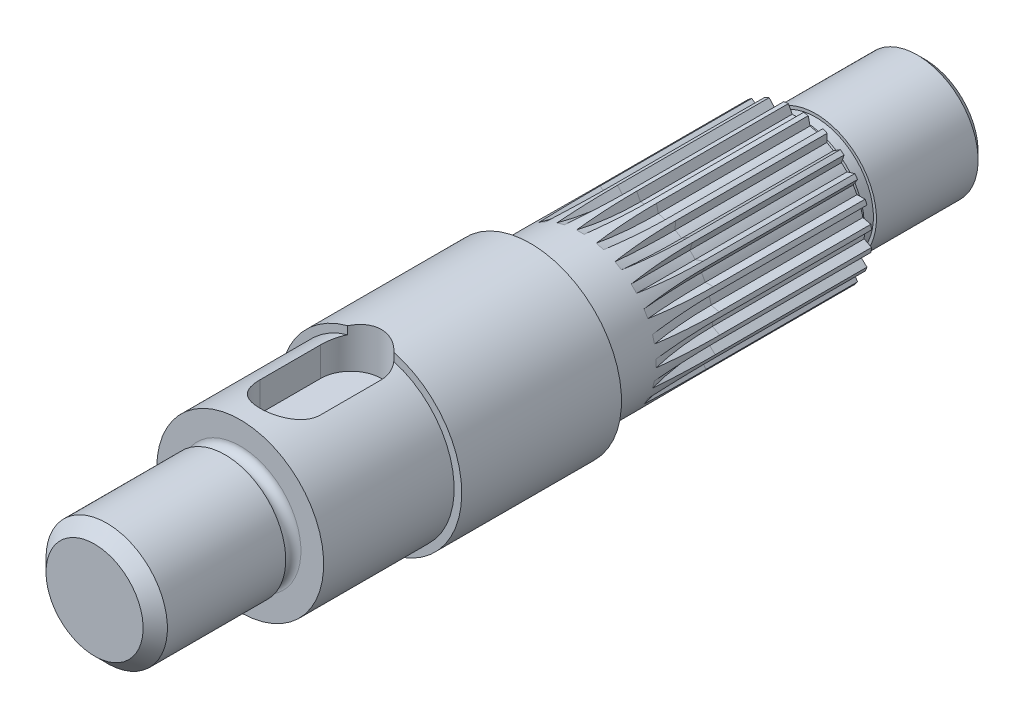
SolidWorks part; units mm, degrees
material "Acier allié"
ref_plane "Plan de face" through (0, 0, 0) normal (0, 0, 1) x (1, 0, 0)
ref_plane "Plan de dessus" through (0, 0, 0) normal (0, 1, 0) x (1, 0, 0)
ref_plane "Plan de droite" through (0, 0, 0) normal (1, 0, 0) x (0, 0, -1)
ref_axis "Axe sortie" through (0, 0, 0) along (0, 0, 1)
sketch "Esquisse1" plane through (0, 0, 0) normal (1, 0, 0) x (0, 0, -1)
  line L0 (0, 0) -> (-70.6218, 0) construction
  line L1 (-63.05, 0) -> (-63.05, 3.2)
  line L2 (-63.05, 3.2) -> (-62.25, 4)
  line L3 (-62.25, 4) -> (-54.45, 4)
  line L4 (-53.45, 4) -> (-53.45, 5.5)
  line L5 (-53.45, 5.5) -> (-44.85, 5.5)
  line L6 (-44.85, 5.5) -> (-44.85, 6)
  line L7 (-44.85, 6) -> (-34.32, 6)
  line L8 (-44.85, 6) -> (-44.85, 10.5) construction
  line L9 (-48.55, 21) -> (-51.45, 21) construction
  line L10 (-53.85, 10.5) -> (-53.85, 5.5) construction
  line L11 (0, 55) -> (0, -55) construction
  line L12 (-48.55, 21) -> (-48.55, 10.5) construction
  line L13 (-48.55, 10.5) -> (-44.85, 10.5) construction
  line L14 (-51.45, 21) -> (-51.45, 10.5) construction
  line L15 (-51.45, 10.5) -> (-53.85, 10.5) construction
  line L16 (-63.05, 0) -> (-8.32, 0)
  line L17 (-8.32, 3.5) -> (-8.32, 0)
  line L18 (-34.32, 6) -> (-34.32, 5)
  line L19 (-34.32, 5) -> (-16.82, 5)
  line L20 (-16.82, 5) -> (-16.82, 4)
  line L21 (-16.82, 4) -> (-16.32, 4)
  line L22 (-8.82, 4) -> (-8.32, 3.5)
  line L23 (-15.52, 4) -> (-8.82, 4)
  line L25 (-16.32, 4) -> (-16.32, 3.8)
  line L26 (-16.32, 3.8) -> (-15.52, 3.8)
  line L27 (-15.52, 4) -> (-15.52, 3.8)
  arc A0 (-54.45, 4) -> (-53.45, 4) centre (-53.95, 4) ccw
  point P12 (-42.45, 6)
  point P16 (-50, 21)
  dimension "D1" = 8
  dimension "D2" = 11
  dimension "D3" = 12
  dimension "D4" = 9.6
  dimension "D5" = 45
  dimension "D6" = 0.8
  dimension "D7" = 8.6
  dimension "D8" = 1
  dimension "D9" = 11
  dimension "D10" = 2.4
  dimension "D11" = 50
  dimension "D12" = 3.7
  dimension "D13" = 9
  dimension "D14" = 21
  dimension "D15" = 42
  dimension "D16" = 45
  dimension "D17" = 10
  dimension "D18" = 8
  dimension "D19" = 8.5
  dimension "D20" = 0.5
  dimension "D21" = 17.5
  dimension "D22" = 10.53
  dimension "D23" = 7.6
  dimension "D24" = 0.8
  dimension "D25" = 0.5
revolve "Révolution1" add sketch "Esquisse1" angle 360 about L0
cosmetic thread "Représentation de filetage1" parameters "D2"=6.619
sketch "Esquisse3" plane through (0, 0, 0) normal (0, 0, 1) x (1, 0, 0)
  line L1 (-2, 7.3) -> (2, 7.3)
  line L2 (-2, 7.3) -> (-2, 3.2)
  line L3 (-2, 3.2) -> (2, 3.2)
  line L4 (2, 7.3) -> (2, 3.2)
  circle A0 centre (0, 0) radius 5.5 construction
  point P7 (0, 7.3)
  dimension "D1" = 12.8
  dimension "D2" = 4
  dimension "D3" = 4.1
  dimension "D4" = 3.2
ref_plane "Plan1" through (0, 3.2, 0) normal (0, 1, 0) x (1, 0, 0)
sketch "Esquisse2" plane through (0, 3.2, 0) normal (0, 1, 0) x (1, 0, 0)
  line L0 (0, -46.15) -> (0, -50.15) construction
  line L1 (2, -46.15) -> (2, -50.15)
  line L2 (-2, -46.15) -> (-2, -50.15)
  line L3 (0, -55) -> (0, 55) construction
  line L4 (-4, -53.45) -> (4, -53.45) construction
  arc A0 (2, -46.15) -> (-2, -46.15) centre (0, -46.15) ccw
  arc A1 (-2, -50.15) -> (2, -50.15) centre (0, -50.15) ccw
  point P3 (0, -48.15)
  dimension "D2" = 8
  dimension "D3" = 1.3
  dimension "D1" = 4
extrude "Enlèv. mat.-Extru.1" cut sketch "Esquisse2" along normal through all
sketch "Esquisse4" plane through (0, 0, 16.82) normal (0, 0, -1) x (-1, 0, 0)
  line L0 (0, 0) -> (0, 6.3174) construction
  line L1 (-0.5, 4.9749) -> (-0.25, 4.4931)
  line L2 (0.5, 4.9749) -> (0.25, 4.4931)
  arc A0 (0.25, 4.4931) -> (-0.25, 4.4931) centre (0, 0) ccw
  arc A1 (0.5, 4.9749) -> (-0.5, 4.9749) centre (0, 0) ccw
  circle A2 centre (0, 0) radius 5 construction
  dimension "D1" = 9
  dimension "D2" = 0.5
  dimension "D3" = 1
sketch "Esquisse5" plane through (0, 0, 0) normal (1, 0, 0) x (0, 0, -1)
  line L0 (-26.82, 4.5) -> (-16.82, 4.5)
  line L3 (-34.32, -6) -> (-34.32, 6) construction
  arc A0 (-26.82, 4.5) -> (-42.9445, 14.5) centre (-26.82, 22.5) cw
  dimension "D1" = 18
  dimension "D2" = 7.5
  dimension "D3" = 10
sweep "Enlèvement de matière-Balayage1" cut profiles "Esquisse4" path "Esquisse5"
pattern_circular "Répétition circulaire1" count 24 over 360 about axis through (0, 0, 0) along (0, 0, 1) of "Enlèvement de matière-Balayage1"
